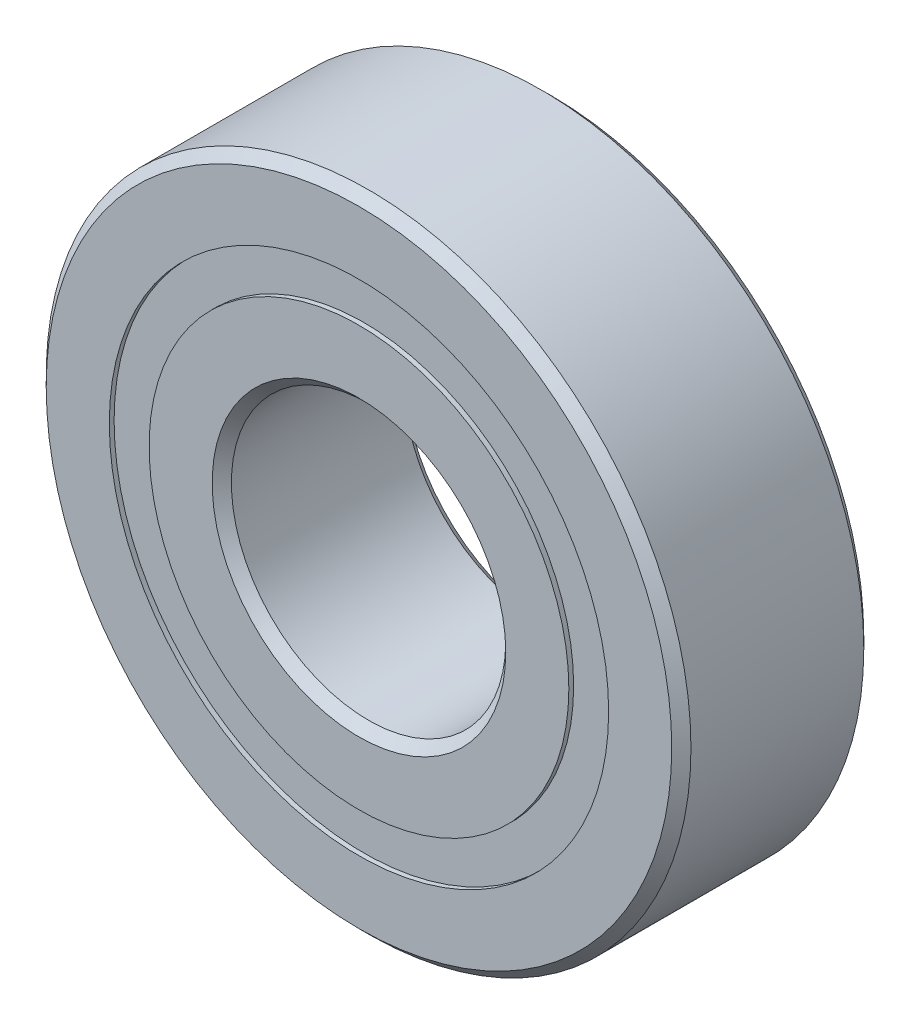
SolidWorks part; units mm, degrees
material "Alloy Steel"
ref_plane "Front Plane" through (0, 0, 0) normal (0, 0, 1) x (1, 0, 0)
ref_plane "Top Plane" through (0, 0, 0) normal (0, 1, 0) x (1, 0, 0)
ref_plane "Right Plane" through (0, 0, 0) normal (1, 0, 0) x (0, 0, -1)
sketch "Sketch1" plane through (0, 0, 0) normal (1, 0, 0) x (0, 0, -1)
  line L0 (-7, 0) -> (7, 0) construction
  line L1 (0, 23.5) -> (0, -23.5) construction
  line L2 (6.3, 23.5) -> (-6.3, 23.5)
  line L3 (-6.3, 23.5) -> (-7, 22.8)
  line L4 (-7, 22.8) -> (-7, 18.2005)
  line L5 (-7, 18.2005) -> (-3.1111, 18.2005)
  line L6 (7, 18.2005) -> (3.1111, 18.2005)
  line L7 (7, 22.8) -> (7, 18.2005)
  line L8 (6.3, 23.5) -> (7, 22.8)
  line L9 (0, 23.5) -> (0, 16.75) construction
  line L10 (0, 16.75) -> (0, 10) construction
  arc A0 (-3.1111, 18.2005) -> (3.1111, 18.2005) centre (0, 16.75) cw
  point P14 (0, 10)
  dimension "Width" = 14
  dimension "OD" = 47
  dimension "D1" = 45
  dimension "D2" = 0.7
  dimension "Shaft Dia" = 20
  dimension "D3" = 6.2222
  dimension "D4" = 1.4505
revolve "Revolve1" add sketch "Sketch1" angle 360 about L0
sketch "Sketch3" plane through (0, 0, 0) normal (1, 0, 0) x (0, 0, -1)
  line L0 (-7, 15.2995) -> (-3.1111, 15.2995)
  line L1 (0, 23.5) -> (0, -23.5) construction
  line L2 (-7, 22.8) -> (-7, 18.2005) construction
  line L3 (-7, 15.2995) -> (-7, 10.7)
  line L4 (-6.3, 23.5) -> (-7, 22.8) construction
  line L5 (-7, 10.7) -> (-6.3, 10)
  line L6 (-6.3, 10) -> (6.3, 10)
  line L7 (6.3, 23.5) -> (6.3, -23.5) construction
  line L8 (6.3, 10) -> (7, 10.7)
  line L9 (7, -22.8) -> (7, 22.8) construction
  line L10 (7, 10.7) -> (7, 15.2995)
  line L11 (7, 15.2995) -> (3.1111, 15.2995)
  line L13 (6.3, 23.5) -> (7, 22.8) construction
  arc A0 (3.1111, 18.2005) -> (-3.1111, 18.2005) centre (0, 16.75) ccw construction
  arc A1 (3.1111, 15.2995) -> (-3.1111, 15.2995) centre (0, 16.75) cw
revolve "Revolve3" add sketch "Sketch3" angle 360 about L0
sketch "Sketch4" plane through (0, 0, 0) normal (1, 0, 0) x (0, 0, -1)
  line L0 (-3.4327, 16.75) -> (3.4327, 16.75)
  arc A2 (-3.4327, 16.75) -> (3.4327, 16.75) centre (0, 16.75) cw
  arc A3 (3.1111, 18.2005) -> (-3.1111, 18.2005) centre (0, 16.75) ccw construction
revolve "Revolve4" add sketch "Sketch4" angle 360 about L0
ref_axis "Axis1" through (0, 0, -7) along (0, 0, 1)
pattern_circular "CirPattern1" count 12 every 30 about axis through (0, 0, -7) along (0, 0, 1) of bodies 104
sketch "Sketch5" plane through (0, 0, 0) normal (1, 0, 0) x (0, 0, -1)
  line L0 (-7, 18.2005) -> (-3.1111, 18.2005) construction
  line L1 (-6.65, 18.2005) -> (-3.4327, 18.2005)
  line L2 (-6.65, 18.2005) -> (-6.65, 15.2995)
  line L3 (-6.65, 15.2995) -> (-3.4327, 15.2995)
  line L4 (-3.4327, 18.2005) -> (-3.4327, 15.2995)
  line L5 (-7, 15.2995) -> (-3.1111, 15.2995) construction
  line L6 (7, 18.2005) -> (3.1111, 18.2005) construction
  line L7 (6.65, 18.2005) -> (3.4327, 18.2005)
  line L8 (6.65, 18.2005) -> (6.65, 15.2995)
  line L9 (6.65, 15.2995) -> (3.4327, 15.2995)
  line L10 (3.4327, 18.2005) -> (3.4327, 15.2995)
  line L11 (7, 15.2995) -> (3.1111, 15.2995) construction
  line L12 (-6.3, 23.5) -> (-7, 22.8) construction
  point P18 (-6.65, 23.15)
revolve "Revolve5" add sketch "Sketch5" angle 360 about L0
equation "\"D2@Sketch1\" = \"Width@Sketch1\"*.05"
equation "\"D3@Sketch1\" = \"Width@Sketch1\"/2.25"
equation "\"D4@Sketch1\" = (((\"OD@Sketch1\"-\"Width@Sketch1\")/2)/3.25)/3.5"
equation "\"D2@CirPattern1\" = 360/\"Balls@CirPattern1\""
